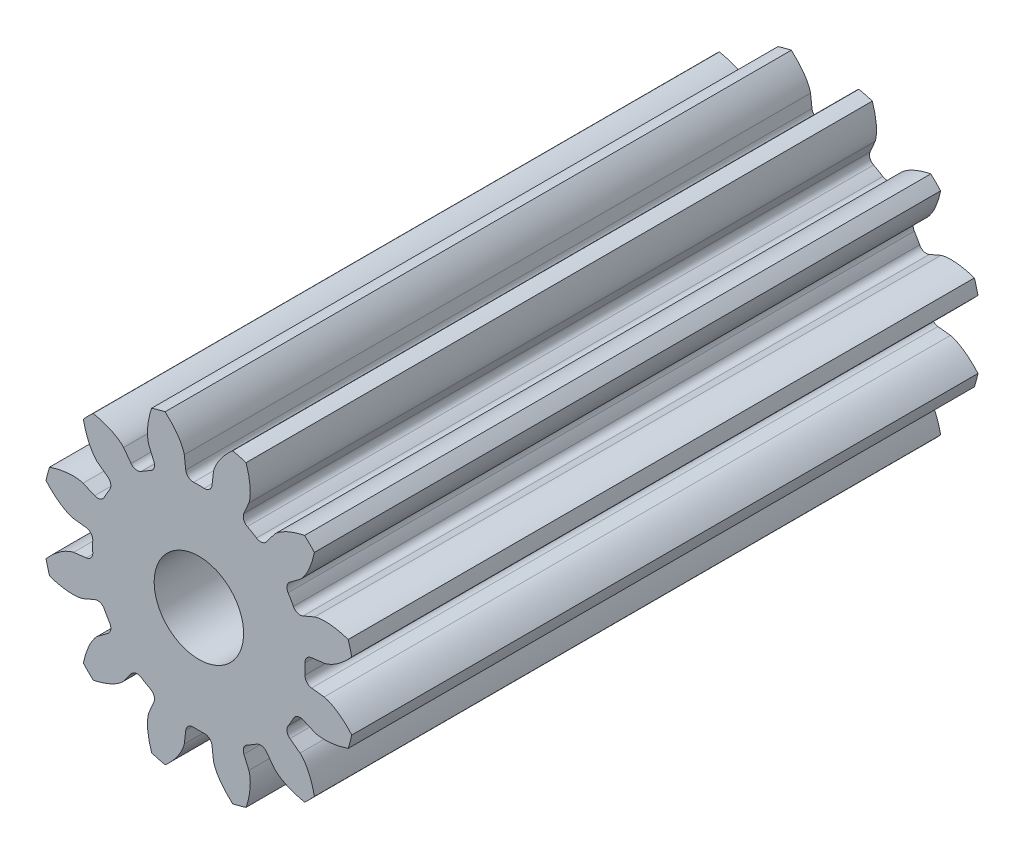
SolidWorks part; units mm, degrees
ref_plane "Front Plane" through (0, 0, 0) normal (0, 0, 1) x (1, 0, 0)
ref_plane "Top Plane" through (0, 0, 0) normal (0, 1, 0) x (1, 0, 0)
ref_plane "Right Plane" through (0, 0, 0) normal (1, 0, 0) x (0, 0, -1)
sketch "Sketch1" plane through (0, 0, 0) normal (0, 0, 1) x (1, 0, 0)
  line L0 (0, 0) -> (0, 4.7625) construction
  line L1 (-1.5306, 5.3196) -> (1.5306, 4.2054) construction
  circle A0 centre (0, 0) radius 3.7703 construction
  circle A1 centre (0, 0) radius 5.5562 construction
  circle A2 centre (0, 0) radius 4.7625 construction
  circle A3 centre (0, 0) radius 4.4753 construction
  point P8 (406.4, 0)
  point P13 (152.4, 0)
  dimension "OD | Outside Diameter" = 11.1125
  dimension "Root Diameter" = 7.5406
  dimension "Gear Pitch Diameter" = 9.525
  dimension "Base Diameter" = 8.9506
  dimension "Pressure Angle" = 20
  dimension "Number of Teeth" = 304.8
  dimension "Gear Pitch | Diametral Pitch" = 812.8
sketch "Sketch2" plane through (0, 0, 0) normal (1, 0, 0) x (0, 0, -1)
  line L0 (-152.4, 0) -> (152.4, 0) construction
  point P2 (-146.8438, 0)
  point P5 (-144.0656, 0)
  point P6 (146.8438, 0)
  dimension "Length" = 304.8
  dimension "D1" = 5.5562
  dimension "D2" = 8.3344
  dimension "D3" = 5.5562
sketch "Sketch3" plane through (0, 0, 0) normal (0, 0, 1) x (1, 0, 0)
  circle A0 centre (0, 0) radius 5.5562
  circle A1 centre (0, 0) radius 5.5562 construction
extrude "Boss-Extrude1" add sketch "Sketch3" against normal up to vertex (152.4 mm away) and the other way up to vertex (152.4 mm away) up to point (0, 0, -152.4) other way up to point (0, 0, 152.4)
sketch "Sketch4" plane through (0, 0, 0) normal (0, 0, 1) x (1, 0, 0)
  line L0 (0, 0) -> (3.745, 0.4364) construction
  line L2 (0, 0) -> (3.745, -0.4364) construction
  line L4 (3.745, 0.4364) -> (4.4452, 0.5179)
  line L5 (4.4452, -0.5179) -> (3.745, -0.4364)
  arc A0 (3.745, 0.4364) -> (3.745, -0.4364) centre (0, 0) cw
  arc A3 (5.4254, 1.1987) -> (5.4254, -1.1987) centre (0, 0) cw
  circle A4 centre (0, 0) radius 5.5562 construction
  spline S0 degree 4 poles (4.4452, 0.5179) (4.447, 0.5182) (4.452, 0.5189) (4.4613, 0.5207) (4.4765, 0.524) (4.4957, 0.5289) (4.5203, 0.5361) (4.5491, 0.5456) (4.5805, 0.5571) (4.6143, 0.5707) (4.6477, 0.5853) (4.6807, 0.6008) (4.7133, 0.6171) (4.7525, 0.6378) (4.799, 0.6639) (4.8525, 0.6964) (4.9122, 0.7355) (4.9721, 0.7778) (5.03, 0.8214) (5.0874, 0.8676) (5.1422, 0.9139) (5.1978, 0.9642) (5.2486, 1.0117) (5.304, 1.0674) (5.3484, 1.113) (5.4053, 1.1756) (5.4385, 1.2134) (5.4767, 1.2584) (5.4934, 1.2789) (5.5037, 1.2914) knots 0 0 0 0 0 0.005377 0.015084 0.028532 0.04661 0.064855 0.092111 0.119476 0.146842 0.174209 0.201575 0.228941 0.256307 0.307035 0.361767 0.4165 0.471232 0.525964 0.580697 0.635429 0.690161 0.744894 0.799626 0.854358 0.909091 0.954545 1 1 1 1 1 construction
  spline S1 degree 4 poles (4.4452, 0.5179) (4.447, 0.5182) (4.452, 0.5189) (4.4613, 0.5207) (4.4765, 0.524) (4.4957, 0.5289) (4.5203, 0.5361) (4.5491, 0.5456) (4.5805, 0.5571) (4.6143, 0.5707) (4.6477, 0.5853) (4.6807, 0.6008) (4.7133, 0.6171) (4.7525, 0.6378) (4.799, 0.6639) (4.8525, 0.6964) (4.9122, 0.7355) (4.9721, 0.7778) (5.03, 0.8214) (5.0874, 0.8676) (5.1422, 0.9139) (5.1978, 0.9642) (5.2486, 1.0117) (5.304, 1.0674) (5.3484, 1.113) (5.393, 1.1621) (5.4145, 1.1862) (5.4254, 1.1987) knots 0 0 0 0 0 0.005377 0.015084 0.028532 0.04661 0.064855 0.092111 0.119476 0.146842 0.174209 0.201575 0.228941 0.256307 0.307035 0.361767 0.4165 0.471232 0.525964 0.580697 0.635429 0.690161 0.744894 0.799626 0.854358 0.909091 0.909091 0.909091 0.909091 0.909091
  spline S2 degree 4 poles (4.4452, -0.5179) (4.447, -0.5182) (4.452, -0.5189) (4.4613, -0.5207) (4.4765, -0.524) (4.4957, -0.5289) (4.5203, -0.5361) (4.5491, -0.5456) (4.5805, -0.5571) (4.6143, -0.5707) (4.6477, -0.5853) (4.6807, -0.6008) (4.7133, -0.6171) (4.7525, -0.6378) (4.799, -0.6639) (4.8525, -0.6964) (4.9122, -0.7355) (4.9721, -0.7778) (5.03, -0.8214) (5.0874, -0.8676) (5.1422, -0.9139) (5.1978, -0.9642) (5.2486, -1.0117) (5.304, -1.0674) (5.3484, -1.113) (5.4053, -1.1756) (5.4385, -1.2134) (5.4767, -1.2584) (5.4934, -1.2789) (5.5037, -1.2914) knots 0 0 0 0 0 0.005377 0.015084 0.028532 0.04661 0.064855 0.092111 0.119476 0.146842 0.174209 0.201575 0.228941 0.256307 0.307035 0.361767 0.4165 0.471232 0.525964 0.580697 0.635429 0.690161 0.744894 0.799626 0.854358 0.909091 0.954545 1 1 1 1 1 construction
  spline S3 degree 4 poles (4.4452, -0.5179) (4.447, -0.5182) (4.452, -0.5189) (4.4613, -0.5207) (4.4765, -0.524) (4.4957, -0.5289) (4.5203, -0.5361) (4.5491, -0.5456) (4.5805, -0.5571) (4.6143, -0.5707) (4.6477, -0.5853) (4.6807, -0.6008) (4.7133, -0.6171) (4.7525, -0.6378) (4.799, -0.6639) (4.8525, -0.6964) (4.9122, -0.7355) (4.9721, -0.7778) (5.03, -0.8214) (5.0874, -0.8676) (5.1422, -0.9139) (5.1978, -0.9642) (5.2486, -1.0117) (5.304, -1.0674) (5.3484, -1.113) (5.393, -1.1621) (5.4145, -1.1862) (5.4254, -1.1987) knots 0 0 0 0 0 0.005377 0.015084 0.028532 0.04661 0.064855 0.092111 0.119476 0.146842 0.174209 0.201575 0.228941 0.256307 0.307035 0.361767 0.4165 0.471232 0.525964 0.580697 0.635429 0.690161 0.744894 0.799626 0.854358 0.909091 0.909091 0.909091 0.909091 0.909091
  dimension "D1" = 7.5406
extrude "Cut-Extrude1" cut sketch "Sketch4" against normal through all both and the other way through all
fillet "Fillet1" radius 0.2663 2 edges at (3.745, -0.4364, 0) (3.745, 0.4364, 0)
pattern_circular "CirPattern1" count 12 over 360 about axis through (0, 0, 152.4) along (0, 0, -1) of "Cut-Extrude1", "Fillet1"
sketch "Sketch6" plane through (0, 0, 152.4) normal (0, 0, 1) x (1, 0, 0)
  circle A0 centre (0, 0) radius 6.35
  dimension "D1" = 12.7
extrude "Cut-Extrude2" cut sketch "Sketch6" against normal blind 282.575
sketch "Sketch7" plane through (0, 0, -152.4) normal (0, 0, -1) x (-1, 0, 0)
  point P0 (0, 0)
hole_wizard "1/8 (0.125) Diameter Hole1" positions "Sketch7" profile "Sketch8" hole size "1/8" standard "ANSI Inch" end condition through all
sketch "Sketch8" plane through (0, 0, -152.4) normal (1, 0, 0) x (0, 1, 0)
  line L0 (0, 0) -> (0, 22.225)
  line L1 (0, 22.225) -> (1.5875, 22.225)
  line L2 (1.5875, 22.225) -> (1.5875, 0)
  line L5 (1.5875, 0) -> (0, 0)
  line L11 (0, -6.35) -> (0, 107.95) construction
  dimension "Thru Hole Dia." = 3.175
  dimension "Thru Hole Depth" = 22.225
equation "\"Root Diameter@Sketch1\"=\"Root Diameter\""
equation "\"OD | Outside Diameter@Sketch1\"=\"Outside Diameter\""
equation "\"D1@CirPattern1\"=\"Number of Teeth\""
equation "\"Diametral Pitch\"=32"
equation "\"Number of Teeth\"=12"
equation "\"Pressure Angle\"=20"
equation "\"Pitch Diameter\"= \"Number of Teeth\" / \"Diametral Pitch\""
equation "\"Base Diameter\"= \"Pitch Diameter\" * cos ( \"Pressure Angle\" )"
equation "\"Outside Diameter\"= ( \"Number of Teeth\" + 2 ) / \"Diametral Pitch\""
equation "\"Dedendum\"= 1.25 / \"Diametral Pitch\""
equation "\"Root Diameter\"= \"Pitch Diameter\" - ( 2 * \"Dedendum\" )"
equation "\"Pitch Angle\"= 360deg / \"Number of Teeth\""
equation "\"Alpha\"= sqr ( \"Pitch Diameter\" ^ 2 - \"Base Diameter\" ^ 2 ) / \"Base Diameter\" * 180 / PI - \"Pressure Angle\""
equation "\"Beta\"= ( \"Pitch Angle\" / 4 - \"Alpha\" )"
equation "\"Phi\"= sqr ( ( \"Outside Diameter\" / 2 ) ^ 2 - ( \"Base Diameter\" / 2 ) ^ 2 ) / ( \"Base Diameter\" / 2 )"
equation "\"Addendum\"= 1 / \"Diametral Pitch\""
equation "\"WorkingDepth\"= 2 / \"Diametral Pitch\""
equation "\"WholeDepth\"= 2.25 / \"Diametral Pitch\""
equation "\"Clearance\"= 0.25 / \"Diametral Pitch\""
equation "\"ToothThickness\"= ( pi * 2 ) / \"Diametral Pitch\""
equation "\"CircularPitch\"= pi / \"Diametral Pitch\""
equation "\"Number of Teeth@Sketch1\"=\"Number of Teeth\""
equation "\"Gear Pitch | Diametral Pitch@Sketch1\"=\"Diametral Pitch\""
equation "\"Pressure Angle@Sketch1\"=\"Pressure Angle\""
equation "\"Gear Pitch Diameter@Sketch1\"=\"Pitch Diameter\""
equation "\"Base Diameter@Sketch1\"=\"Base Diameter\""
equation "\"Fillet\"= \"Clearance\" * cos ( \"Pressure Angle\" ) * tan ( ( 90 + \"Pressure Angle\" ) / 2 )"
equation "\"D1@Fillet1\"=\"Fillet\""
equation "\"D1@Sketch4\"=if( \"Base Diameter\">\"Root Diameter\",\"Root Diameter\",\"Base Diameter\"-.00001)"
equation "\"D1@Sketch2\"=\"OD | Outside Diameter@Sketch1\"*2*0.5*0.5"
equation "\"D2@Sketch2\"=\"D1@Sketch2\"*1.5"
equation "\"D3@Sketch2\"=\"D1@Sketch2\""
